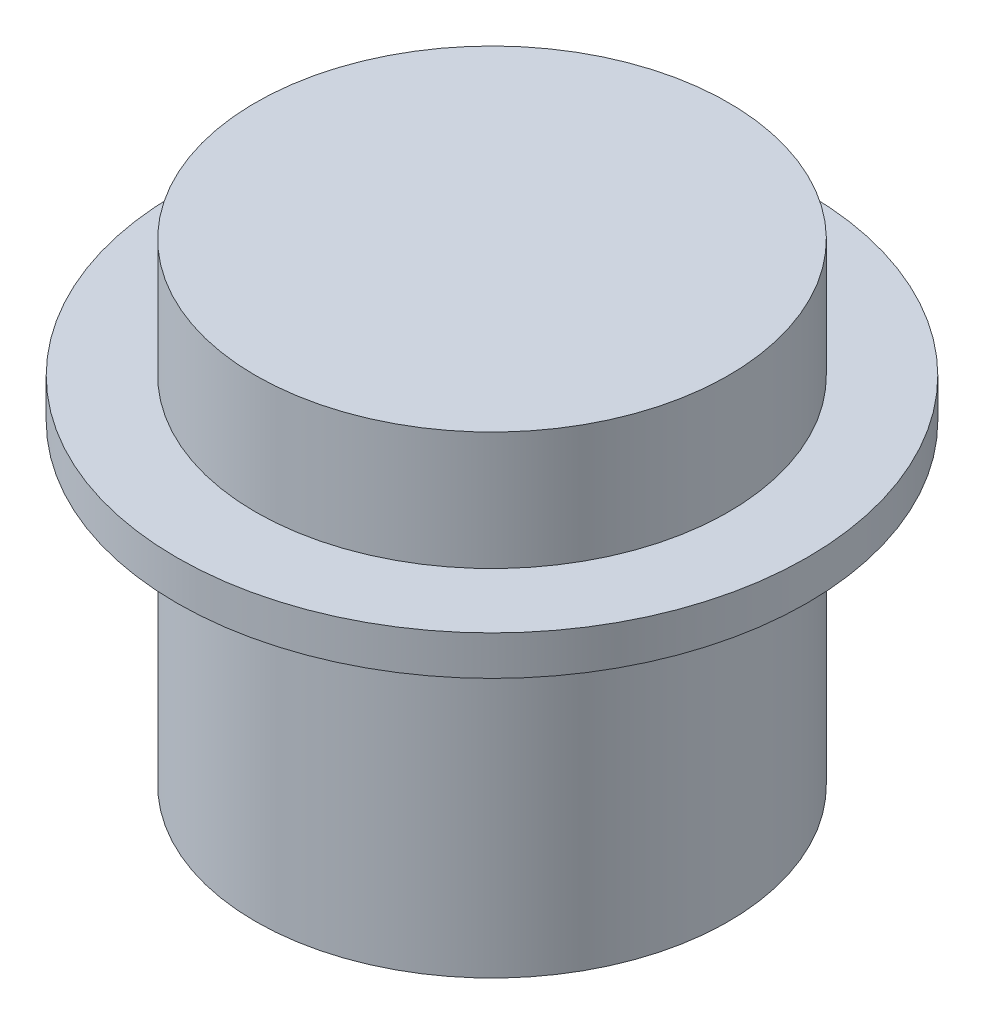
SolidWorks part; units mm, degrees
ref_plane "Front Plane" through (0, 0, 0) normal (0, 0, 1) x (1, 0, 0)
ref_plane "Top Plane" through (0, 0, 0) normal (0, 1, 0) x (1, 0, 0)
ref_plane "Right Plane" through (0, 0, 0) normal (1, 0, 0) x (0, 0, -1)
sketch "Sketch1" plane through (0, 0, 0) normal (0, 1, 0) x (1, 0, 0)
  circle A0 centre (0, 0) radius 50.8
  circle A1 centre (0, 0) radius 38.1
  dimension "D1" = 101.6
  dimension "D2" = 76.2
extrude "Boss-Extrude1" add sketch "Sketch1" along normal blind 25.4 and the other way blind 50.8 contours A1 region at (0, 0, 0)
extrude "Boss-Extrude2" add sketch "Sketch1<3>" along normal blind 6.35
sketch "Sketch1<3>" plane through (0, 0, 0) normal (0, 1, 0) x (1, 0, 0) same geometry as "Sketch1"
